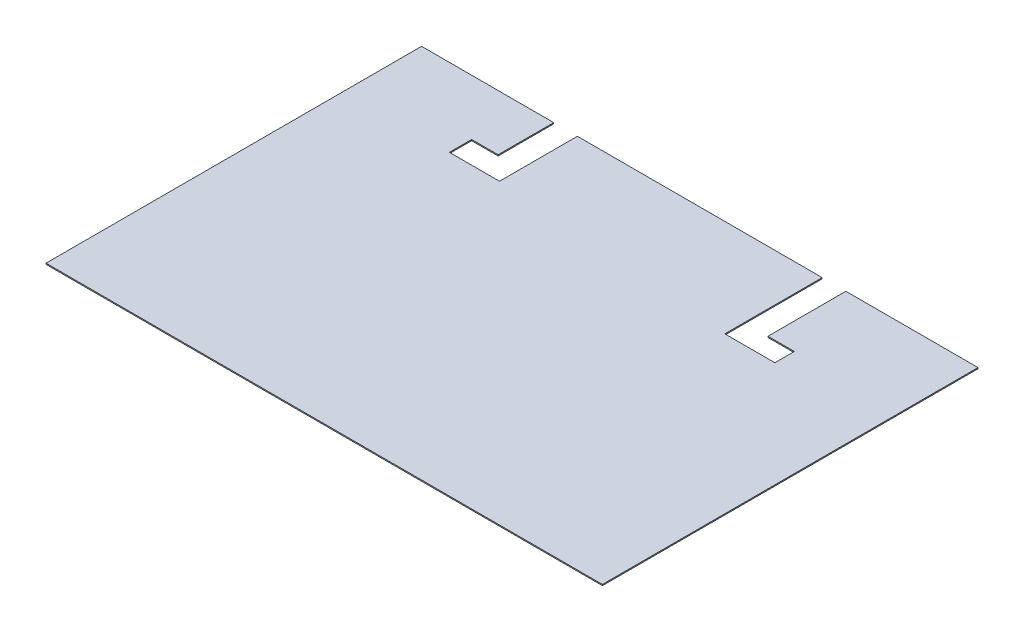
SolidWorks part; units mm, degrees
ref_plane "Front Plane" through (0, 0, 0) normal (0, 0, 1) x (1, 0, 0)
ref_plane "Top Plane" through (0, 0, 0) normal (0, 1, 0) x (1, 0, 0)
ref_plane "Right Plane" through (0, 0, 0) normal (1, 0, 0) x (0, 0, -1)
sketch "Sketch1" plane through (0, 0, 0) normal (0, 1, 0) x (1, 0, 0)
  line L1 (0, 0) -> (25.4, 0)
  line L2 (0, 0) -> (0, 17.145)
  line L3 (0, 17.145) -> (25.4, 17.145)
  line L4 (25.4, 0) -> (25.4, 17.145)
  dimension "D1" = 25.4
  dimension "D2" = 17.145
extrude "Boss-Extrude1" add sketch "Sketch1" along normal blind 0.0508
sketch "Sketch2" plane through (0, 0.0508, 0) normal (0, 1, 0) x (1, 0, 0)
  line L0 (25.4, 17.145) -> (0, 17.145) construction
  line L1 (6.0325, 17.145) -> (7.112, 17.145)
  line L2 (4.826, 14.605) -> (4.826, 13.589)
  line L3 (4.826, 13.589) -> (7.112, 13.589)
  line L4 (7.112, 17.145) -> (7.112, 13.589)
  line L5 (0, 0) -> (25.4, 0) construction
  line L6 (18.288, 17.145) -> (19.3675, 17.145)
  line L7 (18.288, 17.145) -> (18.288, 12.7)
  line L8 (18.288, 12.7) -> (20.574, 12.7)
  line L9 (20.574, 13.589) -> (20.574, 12.7)
  line L10 (0, 0) -> (25.4, 0) construction
  line L11 (19.3675, 13.589) -> (19.3675, 17.145)
  line L12 (19.3675, 13.589) -> (20.574, 13.589)
  line L13 (6.0325, 14.605) -> (6.0325, 17.145)
  line L14 (6.0325, 14.605) -> (4.826, 14.605)
  point P10 (12.7, 0)
  point P13 (12.7, 0)
  point P16 (12.7, 0)
  point P19 (12.7, 0)
  dimension "D1" = 3.556
  dimension "D3" = 2.286
  dimension "D4" = 2.286
  dimension "D5" = 5.588
  dimension "D6" = 5.588
  dimension "D7" = 0
  dimension "D8" = 6.6675
  dimension "D9" = 2.54
  dimension "D10" = 6.6675
extrude "Cut-Extrude1" cut sketch "Sketch2" against normal through all
